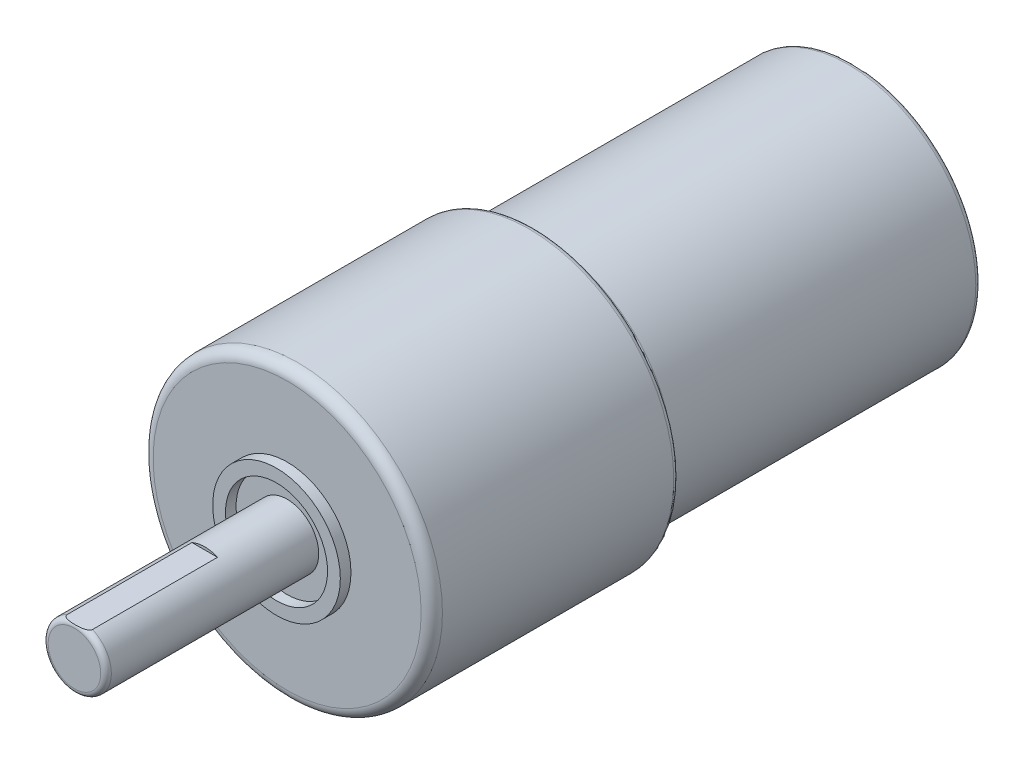
SolidWorks part; units mm, degrees
ref_plane "Front Plane" through (0, 0, 0) normal (0, 0, 1) x (1, 0, 0)
ref_plane "Top Plane" through (0, 0, 0) normal (0, 1, 0) x (1, 0, 0)
ref_plane "Right Plane" through (0, 0, 0) normal (1, 0, 0) x (0, 0, -1)
sketch "Sketch1" plane through (0, 0, 0) normal (0, 0, 1) x (1, 0, 0)
  circle A0 centre (0, 0) radius 13.6
  dimension "D1" = 27.2
extrude "Boss-Extrude1" add sketch "Sketch1" against normal blind 23.25
sketch "Sketch2" plane through (0, 0, -23.25) normal (0, 0, -1) x (-1, 0, 0)
  circle A0 centre (0, 0) radius 12
  dimension "D1" = 24
extrude "Boss-Extrude2" add sketch "Sketch2" along normal blind 30 separate body
fillet "Fillet1" radius 1 1 edges at (-12, 0, -23.25)
fillet "Fillet2" radius 1 1 edges at (13.6, 0, 0)
sketch "Sketch3" plane through (0, 0, 0) normal (0, 0, 1) x (1, 0, 0)
  circle A0 centre (0, 0) radius 6
  circle A1 centre (0, 0) radius 4.8
  dimension "D1" = 12
  dimension "D2" = 9.6
extrude "Boss-Extrude3" add sketch "Sketch3" along normal blind 1
sketch "Sketch4" plane through (0, 0, 0) normal (0, 0, 1) x (1, 0, 0)
  circle A0 centre (0, 0) radius 2.97
  dimension "D1" = 5.94
extrude "Boss-Extrude4" add sketch "Sketch4" along normal blind 20
sketch "Sketch5" plane through (0, 0, 20) normal (0, 0, 1) x (1, 0, 0)
  line L0 (-1.204, 2.715) -> (1.204, 2.715)
  circle A0 centre (0, 0) radius 2.97 construction
  circle A1 centre (0, 0) radius 2.97 construction
  circle M2 centre (0, 0) radius 2.97
  dimension "D1" = 2.715
extrude "Cut-Extrude1" cut sketch "Sketch5" against normal blind 12.25 and the other way through all contours L0 M2 region at (0, 2.8174, 20)
fillet "Fillet3" radius 0.5 1 edges at (0, -2.97, 20)
fillet "Fillet4" radius 0.5 1 edges at (13.6, 0, -23.25)
fillet "Fillet5" radius 0.5 1 edges at (-12, 0, -53.25)
equation "\"D2@Sketch3\"=\"D1@Sketch3\"-2.4"
